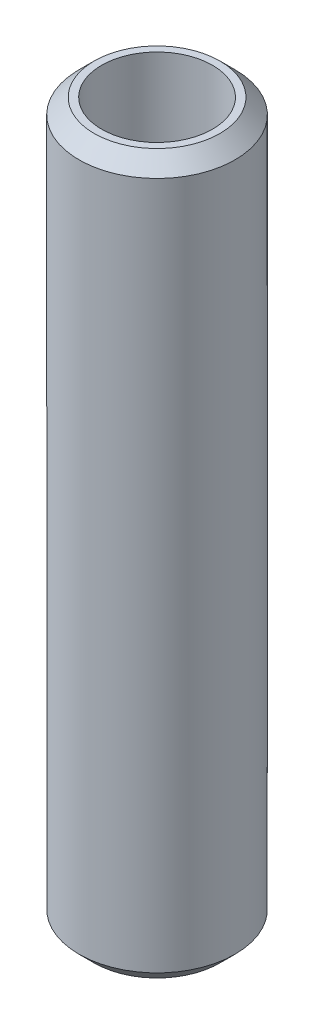
SolidWorks part; units mm, degrees
ref_plane "Front Plane" through (0, 0, 0) normal (0, 0, 1) x (1, 0, 0)
ref_plane "Top Plane" through (0, 0, 0) normal (0, 1, 0) x (1, 0, 0)
ref_plane "Right Plane" through (0, 0, 0) normal (1, 0, 0) x (0, 0, -1)
sketch "Sketch1" plane through (0, 0, 0) normal (0, 1, 0) x (1, 0, 0)
  circle A0 centre (0, 0) radius 15
  dimension "SHAFT_OD" = 30
extrude "Boss-Extrude1" add sketch "Sketch1" along normal blind 138.0519
sketch "Sketch2" plane through (0, 0, 0) normal (0, 1, 0) x (1, 0, 0)
  circle A0 centre (0, 0) radius 10.6575
  dimension "BORE_D" = 21.315
extrude "Cut-Extrude1" cut sketch "Sketch2" along normal through all
chamfer "Chamfer1" distance 2.9194 angle 45 2 edges at (0, 138.0519, 15) (0, 0, 15)
